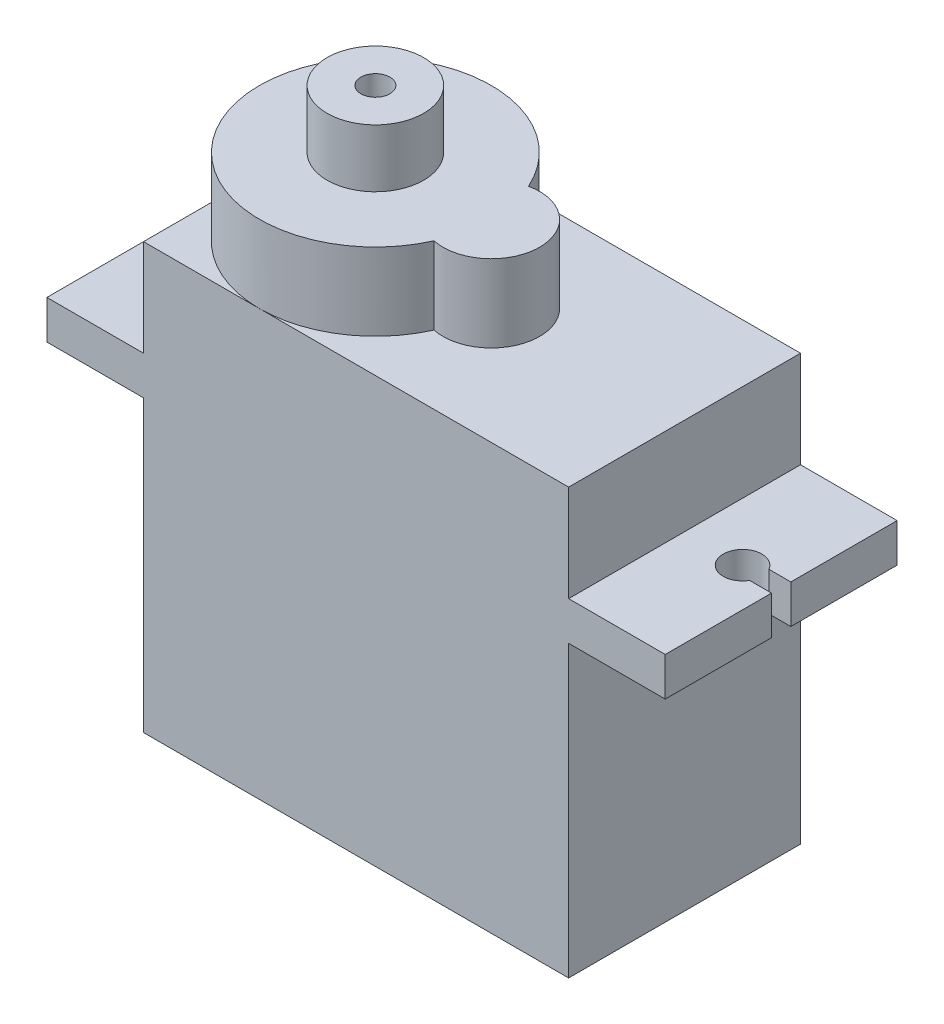
SolidWorks part; units mm, degrees
ref_plane "Front Plane" through (0, 0, 0) normal (0, 0, 1) x (1, 0, 0)
ref_plane "Top Plane" through (0, 0, 0) normal (0, 1, 0) x (1, 0, 0)
ref_plane "Right Plane" through (0, 0, 0) normal (1, 0, 0) x (0, 0, -1)
sketch "Sketch1" plane through (0, 0, 0) normal (0, 1, 0) x (1, 0, 0)
  line L1 (-11, 6) -> (11, 6)
  line L2 (-11, 6) -> (-11, -6)
  line L3 (-11, -6) -> (11, -6)
  line L4 (11, 6) -> (11, -6)
  line L5 (-11, 6) -> (11, -6) construction
  line L6 (-11, -6) -> (11, 6) construction
  point P0 (0, 0)
  dimension "D1" = 22
  dimension "D2" = 12
extrude "Boss-Extrude1" add sketch "Sketch1" along normal blind 22
sketch "Sketch2" plane through (0, 22, 0) normal (0, 1, 0) x (1, 0, 0)
  line L0 (11, 6) -> (-11, 6) construction
  line L1 (-11, 6) -> (-11, -6) construction
  line L2 (-11, -6) -> (11, -6) construction
  line L3 (0, 0) -> (2, 0) construction
  arc A0 (0.4792, 2.4451) -> (0.4792, -2.4451) centre (-5, 0) ccw
  arc A1 (0.4792, -2.4451) -> (0.4792, 2.4451) centre (1, 0) ccw
  dimension "D1" = 5
  dimension "D2" = 12
extrude "Boss-Extrude2" add sketch "Sketch2" along normal blind 4
sketch "Sketch3" plane through (0, 0, 6) normal (0, 0, 1) x (1, 0, 0)
  line L0 (11, 22) -> (11, 0) construction
  line L1 (11, 17) -> (16, 17)
  line L2 (11, 17) -> (11, 15)
  line L3 (11, 15) -> (16, 15)
  line L4 (16, 17) -> (16, 15)
  line L5 (-11, 0) -> (11, 0) construction
  dimension "D1" = 5
  dimension "D2" = 2
  dimension "D3" = 15
extrude "Boss-Extrude3" add sketch "Sketch3" against normal up to surface (12 mm away) up to face at (-1, 13.2, -6)
sketch "Sketch4" plane through (0, 17, 0) normal (0, 1, 0) x (1, 0, 0)
  line L0 (14.866, 0.5) -> (16, 0.5)
  line L1 (16, 6) -> (16, -6) construction
  line L2 (16, 0.5) -> (16, -0.5)
  line L3 (16, -0.5) -> (14.866, -0.5)
  line L4 (16, 0) -> (15, 0) construction
  line L5 (11, -6) -> (11, 6) construction
  line L6 (13, 0) -> (11, 0) construction
  arc A0 (14.866, 0.5) -> (14.866, -0.5) centre (14, 0) ccw
  dimension "D1" = 2
  dimension "D2" = 2
  dimension "D3" = 1
  dimension "D4" = 0.5
extrude "Cut-Extrude1" cut sketch "Sketch4" against normal up to next
mirror "Mirror1" about plane through (0, 0, 0) normal (1, 0, 0) of "Boss-Extrude3", "Cut-Extrude1"
sketch "Sketch5" plane through (0, 26, 0) normal (0, 1, 0) x (1, 0, 0)
  line L0 (-5, 6) -> (-5, -6) construction
  line L1 (-5, 6) -> (-11, 6) construction
  circle A0 centre (-5, 0) radius 2.5
  circle A1 centre (-5, 0) radius 0.75
  arc A2 (0.4792, 2.4451) -> (0.4792, -2.4451) centre (-5, 0) ccw construction
  point P13 (-5, 0)
  dimension "D1" = 5
  dimension "D2" = 1.5
extrude "Boss-Extrude4" add sketch "Sketch5" along normal blind 3
equation "\"D4@Sketch4\"=\"D3@Sketch4\"/2"
